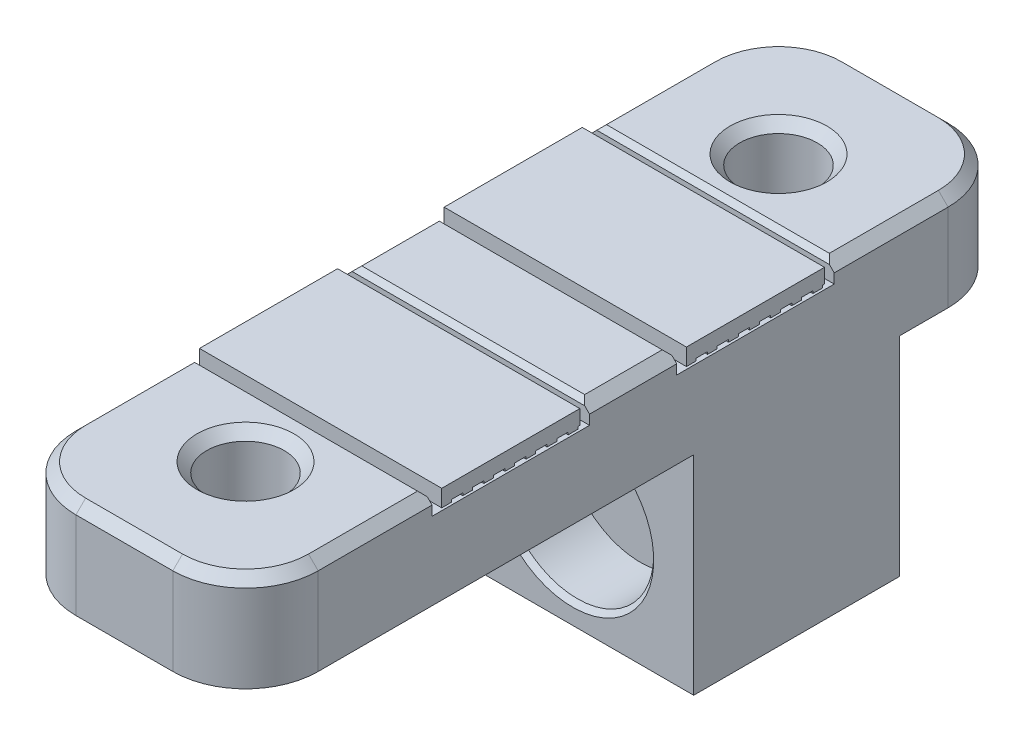
SolidWorks part; units mm, degrees
ref_plane "前视基准面" through (0, 0, 0) normal (0, 0, 1) x (1, 0, 0)
ref_plane "上视基准面" through (0, 0, 0) normal (0, 1, 0) x (1, 0, 0)
ref_plane "右视基准面" through (0, 0, 0) normal (1, 0, 0) x (0, 0, -1)
other "Configuration Table"
sketch "草图1" plane through (0, 0, 0) normal (0, 1, 0) x (1, 0, 0)
  line L1 (0, 0) -> (10, 0)
  line L2 (0, 0) -> (0, 32)
  line L3 (0, 32) -> (10, 32)
  line L4 (10, 0) -> (10, 32)
  circle A0 centre (5, 27) radius 1.6
  circle A1 centre (5, 5) radius 1.6
  point P7 (10, 16)
  dimension "D3" = 3.2
  dimension "D5" = 11
  dimension "D1" = 10
  dimension "D2" = 32
  dimension "D4" = 2
extrude "凸台-拉伸1" add sketch "草图1" along normal blind 4
sketch "草图2" plane through (0, 0, 0) normal (0, -1, 0) x (-1, 0, 0)
  line L0 (0, 32) -> (0, 0) construction
  line L1 (0, 18.5) -> (-10, 18.5)
  line L2 (0, 18.5) -> (0, 27)
  line L3 (0, 27) -> (-10, 27)
  line L4 (-10, 18.5) -> (-10, 27)
  line L5 (-10, 0) -> (-10, 32) construction
  circle A0 centre (-5, 27) radius 1.6 construction
  dimension "D1" = 8.5
  dimension "D2" = 0
extrude "凸台-拉伸2" add sketch "草图2" along normal blind 8.6
sketch "草图3" plane through (0, 0, -18.5) normal (0, 0, 1) x (1, 0, 0)
  line L0 (0, -8.6) -> (0, 0) construction
  line L3 (10, -8.6) -> (0, -8.6) construction
  circle A0 centre (5, -4.6) radius 3.15
  dimension "D1" = 6.3
  dimension "D3" = 4
  dimension "D2" = 5
extrude "切除-拉伸1" cut sketch "草图3" against normal blind 2.8
sketch "草图4" plane through (0, 0, 0) normal (0, -1, 0) x (-1, 0, 0)
  line L0 (0, 27) -> (-10, 27) construction
  circle A0 centre (-5, 27) radius 3
  dimension "D1" = 6
extrude "切除-拉伸2" cut sketch "草图4" along normal through all
sketch "草图5" plane through (0, 4, 0) normal (0, 1, 0) x (1, 0, 0)
  line L0 (0, 32) -> (0, 0) construction
  line L1 (0, 24.3) -> (10, 24.3)
  line L2 (0, 24.3) -> (0, 17.8)
  line L3 (0, 17.8) -> (10, 17.8)
  line L4 (10, 24.3) -> (10, 17.8)
  line L5 (10, 0) -> (10, 32) construction
  line L7 (0, 14.2) -> (10, 14.2)
  line L8 (0, 14.2) -> (0, 7.7)
  line L9 (0, 7.7) -> (10, 7.7)
  line L10 (10, 14.2) -> (10, 7.7)
  circle A0 centre (5, 27) radius 1.6 construction
  circle A1 centre (5, 5) radius 1.6 construction
  dimension "D1" = 2.7
  dimension "D2" = 2.7
  dimension "D3" = 6.5
  dimension "D4" = 6.5
extrude "切除-拉伸3" cut sketch "草图5" against normal blind 0.8
sketch "草图6" plane through (0, 4, 0) normal (0, 1, 0) x (1, 0, 0)
  line L0 (0, 14.2) -> (0, 7.7) construction
  line L1 (0, 13.8) -> (10, 13.8)
  line L2 (0, 13.8) -> (0, 8.1)
  line L3 (0, 8.1) -> (10, 8.1)
  line L4 (10, 13.8) -> (10, 8.1)
  line L5 (10, 7.7) -> (10, 14.2) construction
  line L6 (0, 24.3) -> (0, 17.8) construction
  line L7 (0, 23.9) -> (10, 23.9)
  line L8 (0, 23.9) -> (0, 18.2)
  line L9 (0, 18.2) -> (10, 18.2)
  line L10 (10, 23.9) -> (10, 18.2)
  line L11 (10, 24.3) -> (0, 24.3) construction
  line L13 (0, 17.8) -> (10, 17.8) construction
  line L14 (10, 14.2) -> (0, 14.2) construction
  line L15 (0, 7.7) -> (10, 7.7) construction
  dimension "D1" = 0.4
  dimension "D2" = 0.4
  dimension "D3" = 0.4
  dimension "D4" = 0.4
extrude "凸台-拉伸3" add sketch "草图6" against normal blind 0.6 separate body
sketch "草图7" plane through (0, 4, 0) normal (0, 1, 0) x (1, 0, 0)
  line L0 (10, 8.1) -> (10, 13.8) construction
  line L1 (0, 8.1) -> (10, 8.1)
  line L2 (0, 8.1) -> (0, 8.5)
  line L3 (0, 8.5) -> (10, 8.5)
  line L4 (10, 8.1) -> (10, 8.5)
  line L5 (10, 18.2) -> (10, 23.9) construction
  line L6 (0, 18.2) -> (10, 18.2)
  line L7 (0, 18.2) -> (0, 18.6)
  line L8 (0, 18.6) -> (10, 18.6)
  line L9 (10, 18.2) -> (10, 18.6)
  line L10 (0, 19.07) -> (0, 19.47)
  line L11 (0, 19.07) -> (10, 19.07)
  line L12 (10, 19.07) -> (10, 19.47)
  line L13 (0, 19.47) -> (10, 19.47)
  line L14 (0, 8.97) -> (0, 9.37)
  line L15 (0, 8.97) -> (10, 8.97)
  line L16 (10, 8.97) -> (10, 9.37)
  line L17 (0, 9.37) -> (10, 9.37)
  line L18 (0, 19.94) -> (0, 20.34)
  line L19 (0, 19.94) -> (10, 19.94)
  line L20 (10, 19.94) -> (10, 20.34)
  line L21 (0, 20.34) -> (10, 20.34)
  line L22 (0, 9.84) -> (0, 10.24)
  line L23 (0, 9.84) -> (10, 9.84)
  line L24 (10, 9.84) -> (10, 10.24)
  line L25 (0, 10.24) -> (10, 10.24)
  line L26 (0, 20.81) -> (0, 21.21)
  line L27 (0, 20.81) -> (10, 20.81)
  line L28 (10, 20.81) -> (10, 21.21)
  line L29 (0, 21.21) -> (10, 21.21)
  line L30 (0, 10.71) -> (0, 11.11)
  line L31 (0, 10.71) -> (10, 10.71)
  line L32 (10, 10.71) -> (10, 11.11)
  line L33 (0, 11.11) -> (10, 11.11)
  line L34 (0, 21.68) -> (0, 22.08)
  line L35 (0, 21.68) -> (10, 21.68)
  line L36 (10, 21.68) -> (10, 22.08)
  line L37 (0, 22.08) -> (10, 22.08)
  line L38 (0, 11.58) -> (0, 11.98)
  line L39 (0, 11.58) -> (10, 11.58)
  line L40 (10, 11.58) -> (10, 11.98)
  line L41 (0, 11.98) -> (10, 11.98)
  line L42 (0, 22.55) -> (0, 22.95)
  line L43 (0, 22.55) -> (10, 22.55)
  line L44 (10, 22.55) -> (10, 22.95)
  line L45 (0, 22.95) -> (10, 22.95)
  line L46 (0, 12.45) -> (0, 12.85)
  line L47 (0, 12.45) -> (10, 12.45)
  line L48 (10, 12.45) -> (10, 12.85)
  line L49 (0, 12.85) -> (10, 12.85)
  line L50 (0, 23.42) -> (0, 23.82)
  line L51 (0, 23.42) -> (10, 23.42)
  line L52 (10, 23.42) -> (10, 23.82)
  line L53 (0, 23.82) -> (10, 23.82)
  line L54 (0, 13.32) -> (0, 13.72)
  line L55 (0, 13.32) -> (10, 13.32)
  line L56 (10, 13.32) -> (10, 13.72)
  line L57 (0, 13.72) -> (10, 13.72)
  dimension "D1" = 0.4
  dimension "D2" = 0.4
  dimension "D3" = 7
extrude "凸台-拉伸4" add sketch "草图7" against normal blind 0.7
sketch "草图8" plane through (0, 0, 0) normal (0, -1, 0) x (-1, 0, 0)
  circle A0 centre (-5, 5) radius 3
  circle A1 centre (-5, 27) radius 3
  dimension "D1" = 6
  dimension "D2" = 6
extrude "切除-拉伸4" cut sketch "草图8" against normal blind 1
fillet "圆角1" radius 3 4 edges at (10, 2, 0) (0, 2, 0) (10, 2, -32) (0, 2, -32)
fillet "圆角3" radius 1 2 edges at (2, -4.3, -27) (8, -4.3, -27)
chamfer "倒角1" distance 0.2 angle 45 4 edges at (5, 4, -24.3) (5, 4, -17.8) (5, 4, -14.2) (5, 4, -7.7)
chamfer "倒角4" distance 0.4 angle 45 14 edges at (10, 4, -26.75) (0, 4, -26.75) (10, 4, -16) (0, 4, -16) (5, 4, -3.4) (0, 4, -5.25) (10, 4, -5.25) (0.8787, 4, -0.8787) (9.1213, 4, -0.8787) (5, 4, 0) (5, 4, -25.4) (9.1213, 4, -31.1213) (5, 4, -32) (0.8787, 4, -31.1213)
chamfer "倒角5" distance 0.2 angle 45 1 edges at (8.15, -4.6, -18.5)
